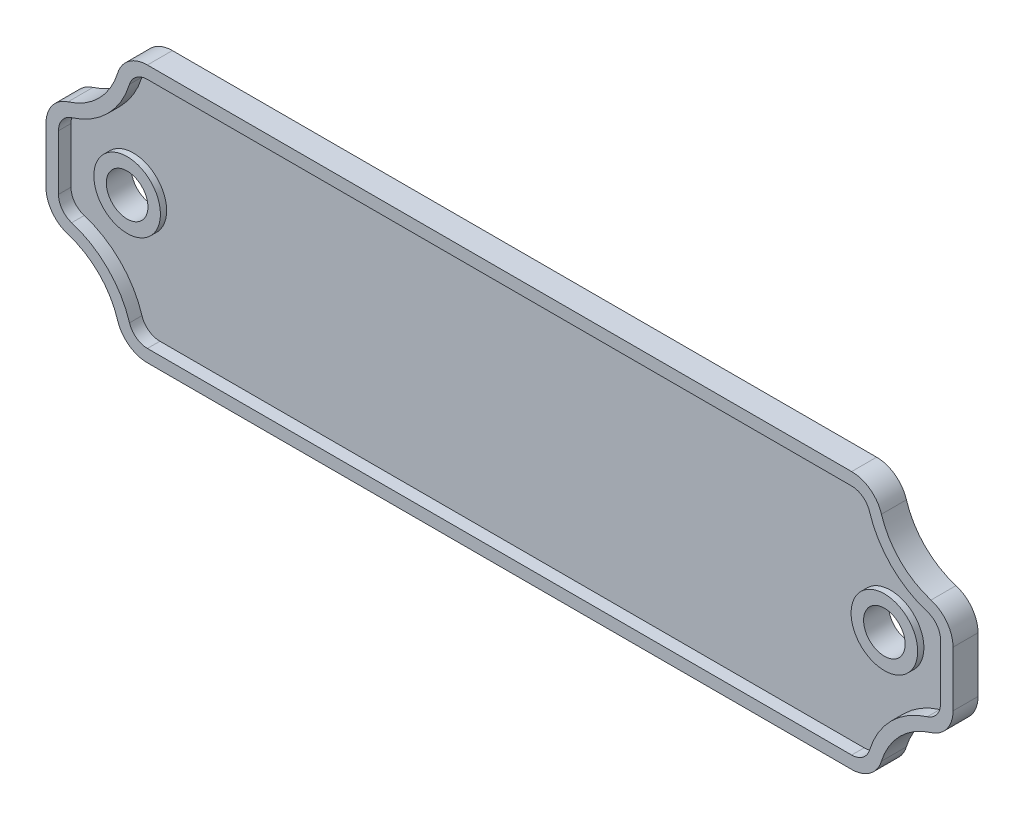
SolidWorks part; units mm, degrees
ref_plane "Front Plane" through (0, 0, 0) normal (0, 0, 1) x (1, 0, 0)
ref_plane "Top Plane" through (0, 0, 0) normal (0, 1, 0) x (1, 0, 0)
ref_plane "Right Plane" through (0, 0, 0) normal (1, 0, 0) x (0, 0, -1)
sketch "Sketch1" plane through (0, 0, 0) normal (0, 0, 1) x (1, 0, 0)
  line L0 (-42.3139, 14) -> (42.3139, 14)
  line L1 (-42.3139, 15.5) -> (42.3139, 15.5)
  line L2 (-54.5, 3.3139) -> (-54.5, -3.3139)
  line L3 (-42.3139, -15.5) -> (42.3139, -15.5)
  line L4 (54.5, 3.3139) -> (54.5, -3.3139)
  line L5 (-45.8433, 13.038) -> (45.8433, -13.038) construction
  line L6 (-45.8433, -13.038) -> (45.8433, 13.038) construction
  line L7 (53, 3.3139) -> (53, -3.3139)
  line L8 (-42.3139, -14) -> (42.3139, -14)
  line L9 (-53, 3.3139) -> (-53, -3.3139)
  arc A0 (-51.8529, 6.8981) -> (-45.8981, 12.8529) centre (-54.5, 15.5) ccw
  arc A1 (-45.8981, -12.8529) -> (-51.8529, -6.8981) centre (-54.5, -15.5) ccw
  arc A2 (51.8529, -6.8981) -> (45.8981, -12.8529) centre (54.5, -15.5) ccw
  arc A3 (45.8981, 12.8529) -> (51.8529, 6.8981) centre (54.5, 15.5) ccw
  arc A4 (51.8529, -6.8981) -> (54.5, -3.3139) centre (50.75, -3.3139) ccw
  arc A5 (-51.8529, 6.8981) -> (-54.5, 3.3139) centre (-50.75, 3.3139) ccw
  arc A6 (-51.8529, -6.8981) -> (-54.5, -3.3139) centre (-50.75, -3.3139) cw
  arc A7 (-45.8981, -12.8529) -> (-42.3139, -15.5) centre (-42.3139, -11.75) ccw
  arc A8 (45.8981, -12.8529) -> (42.3139, -15.5) centre (42.3139, -11.75) cw
  arc A9 (51.8529, 6.8981) -> (54.5, 3.3139) centre (50.75, 3.3139) cw
  arc A10 (45.8981, 12.8529) -> (42.3139, 15.5) centre (42.3139, 11.75) ccw
  arc A11 (-45.8981, 12.8529) -> (-42.3139, 15.5) centre (-42.3139, 11.75) cw
  circle A12 centre (-45.5, 0) radius 4
  circle A13 centre (45.5, 0) radius 4
  arc A14 (44.4644, 12.4118) -> (42.3139, 14) centre (42.3139, 11.75) ccw
  arc A15 (44.4644, 12.4118) -> (51.4118, 5.4644) centre (54.5, 15.5) ccw
  arc A16 (51.4118, 5.4644) -> (53, 3.3139) centre (50.75, 3.3139) cw
  arc A17 (51.4118, -5.4644) -> (53, -3.3139) centre (50.75, -3.3139) ccw
  arc A18 (51.4118, -5.4644) -> (44.4644, -12.4118) centre (54.5, -15.5) ccw
  arc A19 (44.4644, -12.4118) -> (42.3139, -14) centre (42.3139, -11.75) cw
  arc A20 (-44.4644, -12.4118) -> (-42.3139, -14) centre (-42.3139, -11.75) ccw
  arc A21 (-44.4644, -12.4118) -> (-51.4118, -5.4644) centre (-54.5, -15.5) ccw
  arc A22 (-51.4118, -5.4644) -> (-53, -3.3139) centre (-50.75, -3.3139) cw
  arc A23 (-51.4118, 5.4644) -> (-53, 3.3139) centre (-50.75, 3.3139) ccw
  arc A24 (-51.4118, 5.4644) -> (-44.4644, 12.4118) centre (-54.5, 15.5) ccw
  arc A25 (-44.4644, 12.4118) -> (-42.3139, 14) centre (-42.3139, 11.75) cw
  circle A26 centre (-45.5, 0) radius 2.5
  circle A27 centre (45.5, 0) radius 2.5
  point P0 (0, 0)
  point P38 (-54.5, 0)
  dimension "D3" = 18
  dimension "D4" = 18
  dimension "D5" = 18
  dimension "D6" = 18
  dimension "D7" = 3.75
  dimension "D8" = 8
  dimension "D9" = 8
  dimension "D14" = 5
  dimension "D15" = 5
  dimension "D1" = 109
  dimension "D2" = 31
  dimension "D10" = 9
  dimension "D11" = 9
  dimension "D12" = 15.5
  dimension "D13" = 1.5
extrude "Boss-Extrude1" add sketch "Sketch1" along normal blind 1.5 contours A12 | A13 | L0 A14 A15 A16 L7 A17 A18 A19 L8 A20 A21 A22 L9 A23 A24 A25
extrude "Boss-Extrude3" add sketch "Sketch1<4>" along normal blind 2.25 and the other way blind 0.75 contours A12 A26 | A13 A27 region at (-49.3869, 0, 0) region at (41.6131, 0, 0)
sketch "Sketch1<4>" plane through (0, 0, 0) normal (0, 0, 1) x (1, 0, 0) same geometry as "Sketch1"
extrude "Boss-Extrude4" add sketch "Sketch1<5>" along normal blind 3 contours A11 A0 A5 L2 A6 A1 A7 L3 A8 A2 A4 L4 A9 A3 A10 L1 A24 A25 L0 A14 A15 A16 L7 A17 A18 A19 L8 A20 A21 A22 L9 A23 region at (0, 14.3668, 0)
sketch "Sketch1<5>" plane through (0, 0, 0) normal (0, 0, 1) x (1, 0, 0) same geometry as "Sketch1"
